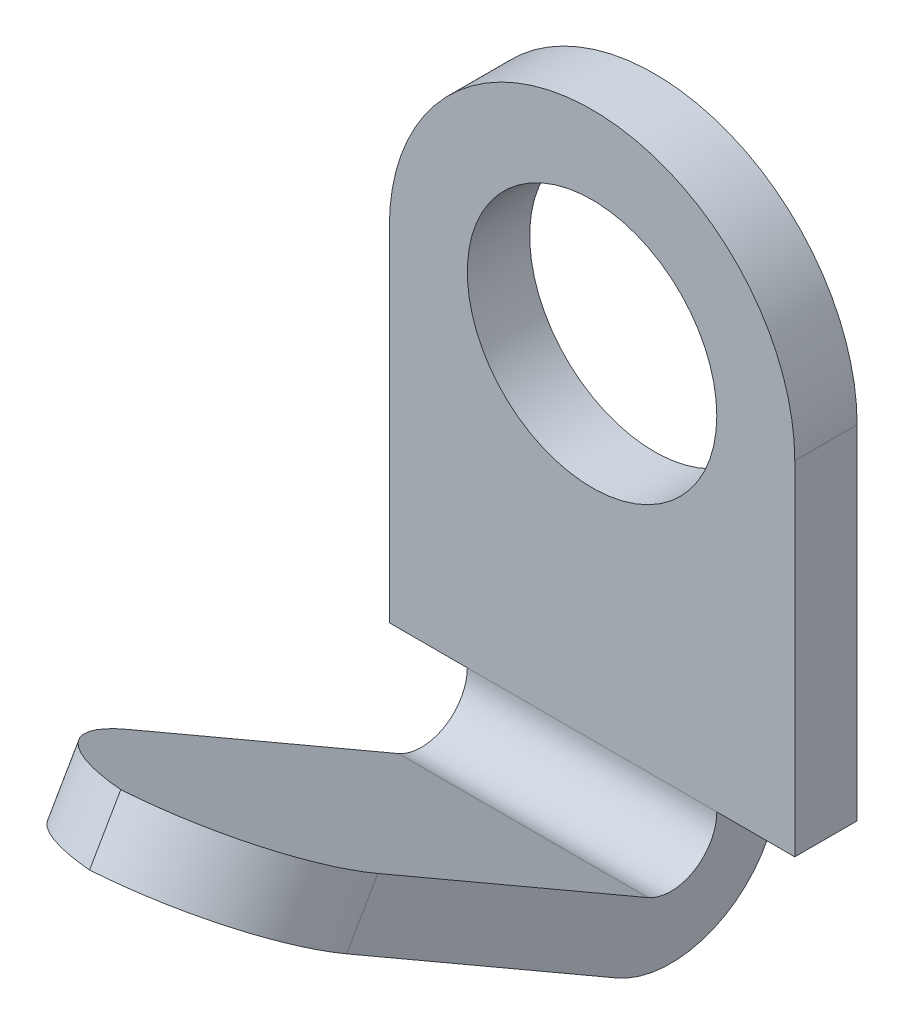
SolidWorks part; units mm, degrees
material "Copper"
ref_plane "Front Plane" through (0, 0, 0) normal (0, 0, 1) x (1, 0, 0)
ref_plane "Top Plane" through (0, 0, 0) normal (0, 1, 0) x (1, 0, 0)
ref_plane "Right Plane" through (0, 0, 0) normal (1, 0, 0) x (0, 0, -1)
sketch "Sketch1" plane through (0, 0, 0) normal (0, 0, 1) x (1, 0, 0)
  line L0 (-0.65, 0) -> (-0.65, -1.1)
  line L1 (-0.65, -1.1) -> (0.65, -1.1)
  line L2 (0.65, -1.1) -> (0.65, 0)
  arc A0 (-0.65, 0) -> (0.65, 0) centre (0, 0) cw
  circle A1 centre (0, 0) radius 0.4
  dimension "D1" = 1.1
  dimension "D3" = 0.8
  dimension "D2" = 1.3
extrude "Boss-Extrude1" add sketch "Sketch1" along normal blind 0.2
sketch "Sketch2" plane through (0, 0, 0) normal (1, 0, 0) x (0, 0, -1)
  line L0 (-0.2, -1.1) -> (0, -1.1) construction
  line L1 (-0.2, -1.1) -> (0, -1.1)
  line L2 (0, -1.1) -> (0, 0) construction
  line L3 (-0.521, -1.4008) -> (-1.82, -0.6508)
  line L5 (-0.421, -1.2276) -> (-1.72, -0.4776)
  line L6 (-1.72, -0.4776) -> (-1.82, -0.6508)
  line L7 (-0.2, -1.1) -> (-0.2, 0) construction
  arc A0 (0, -1.1) -> (-0.521, -1.4008) centre (-0.3473, -1.1) cw
  arc A1 (-0.2, -1.1) -> (-0.421, -1.2276) centre (-0.3473, -1.1) cw
  dimension "D1" = 60
  dimension "D2" = 1.5
  dimension "D3" = 1.62
  dimension "D4" = 0.2
extrude "Boss-Extrude2" add sketch "Sketch2" against normal mid plane 0.8 contours L1 A1 L5 L6 L3 A0 region at (0, -1.0284, 0.8943)
fillet "Fillet2" radius 0.5 2 edges at (0.4, -0.5642, 1.77) (-0.4, -0.5642, 1.77)
